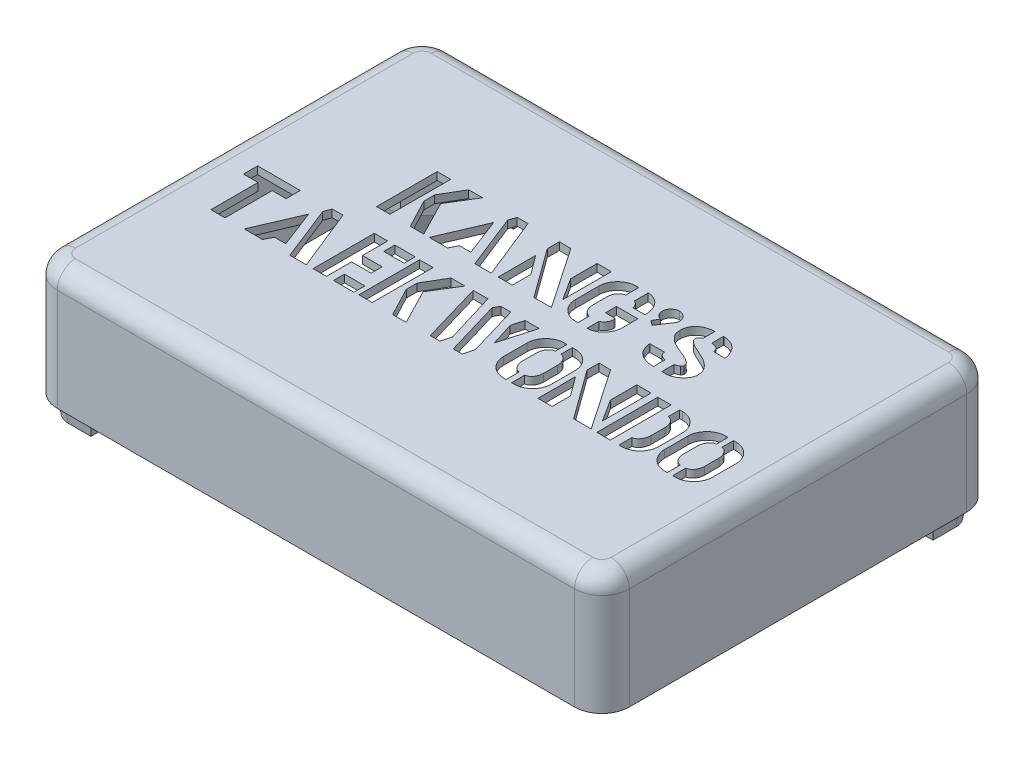
SolidWorks part; units mm, degrees
ref_plane "Front Plane" through (0, 0, 0) normal (0, 0, 1) x (1, 0, 0)
ref_plane "Top Plane" through (0, 0, 0) normal (0, 1, 0) x (1, 0, 0)
ref_plane "Right Plane" through (0, 0, 0) normal (1, 0, 0) x (0, 0, -1)
sketch "Sketch1" plane through (0, 0, 0) normal (0, 1, 0) x (1, 0, 0)
  line L0 (-41.5, -30.5958) -> (-41.5, 24.85)
  line L1 (-37, -33.5958) -> (48, -33.5958)
  line L2 (-40, -30.5958) -> (-40, 24.85)
  line L3 (-37, 27.85) -> (48, 27.85)
  line L4 (51, -30.5958) -> (51, 24.85)
  line L5 (-40, -33.5958) -> (51, 27.85) construction
  line L6 (-40, 27.85) -> (51, -33.5958) construction
  line L7 (-37, 29.35) -> (48, 29.35)
  line L8 (52.5, -30.5958) -> (52.5, 24.85)
  line L9 (-37, -35.0958) -> (48, -35.0958)
  line L12 (-37, 29.35) -> (48, 29.35) construction
  line L13 (48, -35.0958) -> (-37, -35.0958) construction
  line L14 (52.5, 24.85) -> (52.5, -30.5958) construction
  line L15 (-41.5, -30.5958) -> (-41.5, 24.85) construction
  arc A0 (48, -33.5958) -> (51, -30.5958) centre (48, -30.5958) ccw
  arc A1 (-37, -33.5958) -> (-40, -30.5958) centre (-37, -30.5958) cw
  arc A2 (-40, 24.85) -> (-37, 27.85) centre (-37, 24.85) cw
  arc A3 (48, 27.85) -> (51, 24.85) centre (48, 24.85) cw
  arc A4 (-41.5, 24.85) -> (-37, 29.35) centre (-37, 24.85) cw
  arc A5 (48, 29.35) -> (52.5, 24.85) centre (48, 24.85) cw
  arc A6 (48, -35.0958) -> (52.5, -30.5958) centre (48, -30.5958) ccw
  arc A7 (-37, -35.0958) -> (-41.5, -30.5958) centre (-37, -30.5958) cw
  dimension "D1" = 3
  dimension "D2" = 1.5
extrude "Boss-Extrude1" add sketch "Sketch1" along normal blind 1.25 contours A7 L9 A6 L8 A5 L7 A4 L0 L3 A3 L4 A0 L1 A1 L2 A2 | A3 L3 A2 L2 A1 L1 A0 L4 region at (-40.3603, 0, 2.8729) region at (5.5, 0, 2.8729)
extrude "Boss-Extrude2" add sketch "Sketch1<3>" against normal up to surface (18.5512 mm away)
sketch "Sketch1<3>" plane through (0, 0, 0) normal (0, 1, 0) x (1, 0, 0) same geometry as "Sketch1"
sketch "Sketch2" plane through (0, 0, -29.35) normal (0, 0, -1) x (-1, 0, 0)
  line L5 (25.025, -5.0212) -> (-19.705, -5.0212)
  line L6 (25.025, -5.0212) -> (25.025, -18.5512)
  line L7 (25.025, -18.5512) -> (-19.705, -18.5512)
  line L30 (-19.705, -5.0212) -> (-19.705, -18.5512)
  line L32 (-48, -18.5512) -> (37, -18.5512) construction
  line L34 (-40.025, -18.5512) -> (-25.775, -18.5512)
  line L35 (-40.025, -18.5512) -> (-40.025, -5.0212)
  line L36 (24.525, -6.0212) -> (11.275, -6.0212) construction
  line L38 (-40.025, -5.0212) -> (-25.775, -5.0212)
  line L39 (-25.775, -18.5512) -> (-25.775, -5.0212)
  dimension "D2" = 1
  dimension "D3" = 0.5
  dimension "D4" = 0.5
  dimension "D5" = 0.5
  dimension "D1" = 0.5
extrude "Cut-Extrude1" cut sketch "Sketch2" against normal up to next
sketch "Sketch3" plane through (0, 0, 0) normal (0, -1, 0) x (1, 0, 0)
  line L0 (-32.7145, -24.1) -> (-36.25, -20.5645)
  line L1 (-36.25, 26.3103) -> (-32.7145, 29.8458)
  line L2 (43.7145, -24.1) -> (47.25, -20.5645)
  line L3 (48, -28.1) -> (43.7145, -28.1)
  line L4 (43.7145, -28.1) -> (43.7145, -24.1)
  line L5 (51.25, -24.85) -> (51.25, -20.5645)
  line L6 (51.25, -20.5645) -> (47.25, -20.5645)
  line L7 (-37, -28.1) -> (-32.7145, -28.1)
  line L8 (-32.7145, -28.1) -> (-32.7145, -24.1)
  line L9 (-40.25, -24.85) -> (-40.25, -20.5645)
  line L10 (-40.25, -20.5645) -> (-36.25, -20.5645)
  line L11 (-40.25, 30.5958) -> (-40.25, 26.3103)
  line L12 (-40.25, 26.3103) -> (-36.25, 26.3103)
  line L13 (-32.7145, 29.8458) -> (-32.7145, 33.8458)
  line L14 (-32.7145, 33.8458) -> (-37, 33.8458)
  arc A0 (51.25, -24.85) -> (48, -28.1) centre (48, -24.85) cw
  arc A1 (48, -27.85) -> (51, -24.85) centre (48, -24.85) ccw construction
  arc A3 (-37, -28.1) -> (-40.25, -24.85) centre (-37, -24.85) cw
  arc A4 (-40, -24.85) -> (-37, -27.85) centre (-37, -24.85) ccw construction
  arc A5 (-40.25, 30.5958) -> (-37, 33.8458) centre (-37, 30.5958) cw
  arc A6 (-37, 33.5958) -> (-40, 30.5958) centre (-37, 30.5958) ccw construction
  dimension "D1" = 0.25
  dimension "D2" = 5
  dimension "D3" = 4
extrude "Boss-Extrude3" add sketch "Sketch3" along normal up to surface (18.5512 mm away) up to face at (5.9, -18.5512, -3.4217)
extrude "Boss-Extrude4" add sketch "Sketch3<3>" along normal blind 3 draft 10 from surface starting at face at (22.74, -18.5512, -28.6)
sketch "Sketch3<3>" plane through (0, 0, 0) normal (0, -1, 0) x (1, 0, 0) same geometry as "Sketch3"
fillet "Fillet1" radius 3 22 edges at (-40.182, 1.25, -28.032) (-41.5, 1.25, 2.8729) (-40.182, 1.25, 33.7778) (5.5, 1.25, 35.0958) (51.182, 1.25, 33.7778) (52.5, 1.25, 2.8729) (51.182, 1.25, -28.032) (5.5, 1.25, -29.35) (-40, 0, 2.8729) (5.5, 0, -27.85) (51, 0, 5.0157) (50.1213, 0, 32.7171) (7.6428, 0, 33.5958) (-32.7145, 0, -25.975) (-34.4822, 0, -22.3322) (-38.125, 0, -20.5645) (-38.125, 0, 26.3103) (-34.4822, 0, 28.078) (-32.7145, 0, 31.7208) (49.125, 0, -20.5645) (45.4822, 0, -22.3322) (43.7145, 0, -25.975)
sketch "Sketch4" plane through (0, -18.5512, 0) normal (0, -1, 0) x (1, 0, 0)
  line L0 (48, -29.35) -> (40.025, -29.35) construction
  line L1 (37.6139, -29.35) -> (46.45, -29.35)
  line L2 (37.6139, -29.35) -> (37.6139, -21.3645)
  line L3 (37.6139, -21.3645) -> (46.45, -21.3645)
  line L4 (46.45, -29.35) -> (46.45, -21.3645)
  line L6 (47.25, -20.5645) -> (43.7145, -24.1) construction
  line L10 (45.95, -27.85) -> (45.95, -17.0042) construction
  dimension "D1" = 0.5
extrude "Cut-Extrude2" cut sketch "Sketch4" along normal through all
sketch "Sketch5" plane through (0, 1.25, 0) normal (0, 1, 0) x (1, 0, 0)
  line L0 (-38.5, 0) -> (49.5, 0) construction
  line L1 (-38.5, -14) -> (49.5, -14) construction
  line L2 (-38.5, 24.85) -> (-38.5, -30.5958) construction
  line L3 (49.5, -30.5958) -> (49.5, 24.85) construction
  text T0 "KANG'S" font "Stencil Gothic" height 10
  text T1 "TAEKWONDO" font "Stencil Gothic" height 10
  dimension "D1" = 14
extrude "Cut-Extrude3" cut sketch "Sketch5" against normal through all
